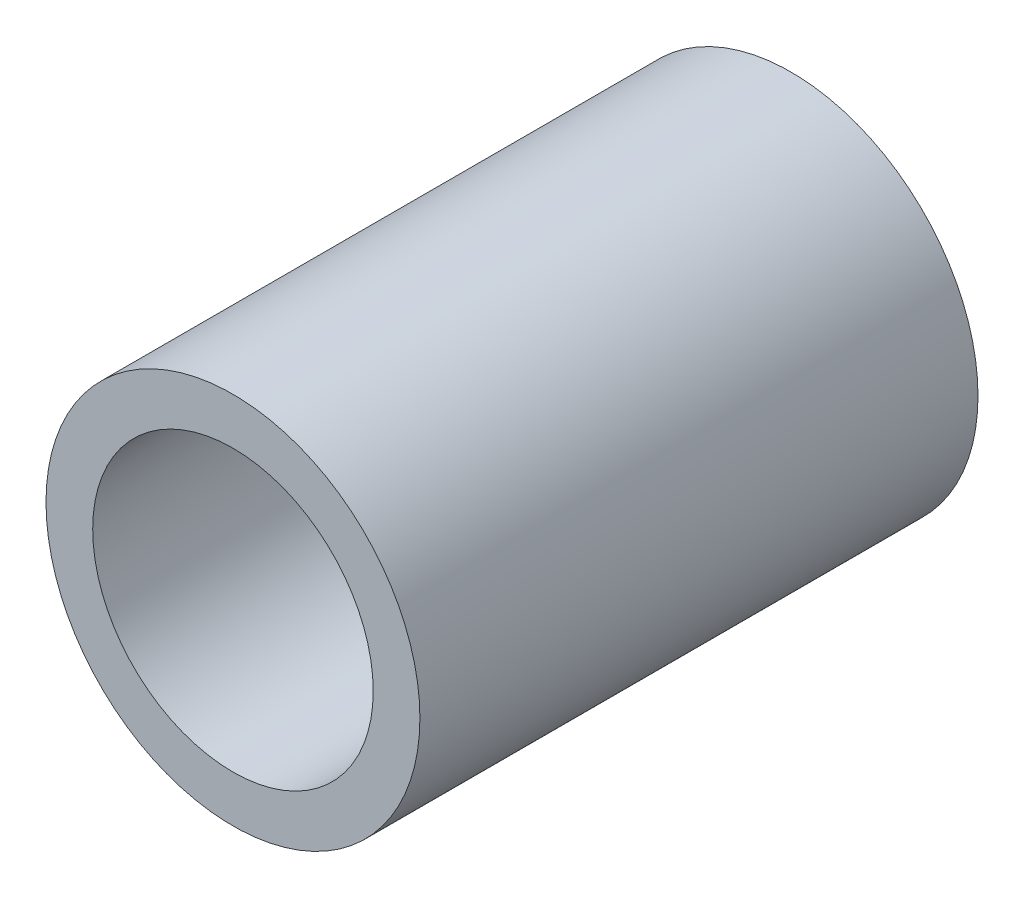
SolidWorks part; units mm, degrees
material "Brass"
ref_plane "Front Plane" through (0, 0, 0) normal (0, 0, 1) x (1, 0, 0)
ref_plane "Top Plane" through (0, 0, 0) normal (0, 1, 0) x (1, 0, 0)
ref_plane "Right Plane" through (0, 0, 0) normal (1, 0, 0) x (0, 0, -1)
sketch "Sketch1" plane through (0, 0, 0) normal (1, 0, 0) x (0, 0, -1)
  line L0 (-9.525, 6.3818) -> (-9.525, 4.7879)
  line L1 (-9.525, 4.7879) -> (9.525, 4.7879)
  line L2 (9.525, 4.7879) -> (9.525, 6.3818)
  line L3 (9.525, 6.3818) -> (-9.525, 6.3818)
  line L4 (9.525, 0) -> (-9.525, 0) construction
revolve "Revolve1" add sketch "Sketch1" angle 360 about L4 reverse direction yes
ref_plane "bushing XY" through (0, 0, 0) normal (0, 0, 1) x (1, 0, 0)
ref_plane "bushing XZ" through (0, 0, 0) normal (0, -1, 0) x (-1, 0, 0)
ref_plane "bushing YZ" through (0, 0, 0) normal (1, 0, 0) x (0, 0, -1)
ref_axis "bushing X" through (-80.9, 0, 0) along (1, 0, 0)
ref_axis "bushing Y" through (0, -50, 0) along (0, 1, 0)
ref_axis "bushing Z" through (0, 0, 80.9) along (0, 0, -1)
sketch3d "bushing"
  point P0 (0, 0, 0)
ref_plane "id1 XY" through (0, 0, 0) normal (0, 0, 1) x (1, 0, 0)
ref_plane "id1 XZ" through (0, 0, 0) normal (0, -1, 0) x (-1, 0, 0)
ref_plane "id1 YZ" through (-4.7879, 0, 0) normal (1, 0, 0) x (0, 0, -1)
ref_axis "id1 X" through (-80.9, 0, 0) along (1, 0, 0)
ref_axis "id1 Y" through (-4.7879, -50, 0) along (0, 1, 0)
ref_axis "id1 Z" through (-4.7879, 0, 80.9) along (0, 0, -1)
sketch3d "id1"
  point P0 (-4.7879, 0, 0)
ref_plane "id2 XY" through (0, 0, 0) normal (0, 0, 1) x (1, 0, 0)
ref_plane "id2 XZ" through (0, 0, 0) normal (0, -1, 0) x (-1, 0, 0)
ref_plane "id2 YZ" through (4.7879, 0, 0) normal (1, 0, 0) x (0, 0, -1)
ref_axis "id2 X" through (-80.9, 0, 0) along (1, 0, 0)
ref_axis "id2 Y" through (4.7879, -50, 0) along (0, 1, 0)
ref_axis "id2 Z" through (4.7879, 0, 80.9) along (0, 0, -1)
sketch3d "id2"
  point P0 (4.7879, 0, 0)
ref_plane "id3 XY" through (0, 0, -9.525) normal (0, 0, -1) x (-1, 0, 0)
ref_plane "id3 XZ" through (0, 0, 0) normal (-1, 0, 0) x (0, 0, 1)
ref_plane "id3 YZ" through (0, 0, 0) normal (0, 1, 0) x (1, 0, 0)
ref_axis "id3 X" through (0, -50, -9.525) along (0, 1, 0)
ref_axis "id3 Y" through (-80.9, 0, -9.525) along (1, 0, 0)
ref_axis "id3 Z" through (0, 0, -50) along (0, 0, 1)
sketch3d "id3"
  point P0 (0, 0, -9.525)
ref_plane "id4 XY" through (0, 0, 9.525) normal (0, 0, 1) x (1, 0, 0)
ref_plane "id4 XZ" through (0, 0, 0) normal (1, 0, 0) x (0, 0, -1)
ref_plane "id4 YZ" through (0, 0, 0) normal (0, 1, 0) x (1, 0, 0)
ref_axis "id4 X" through (0, -50, 9.525) along (0, 1, 0)
ref_axis "id4 Y" through (80.9, 0, 9.525) along (-1, 0, 0)
ref_axis "id4 Z" through (0, 0, 50) along (0, 0, -1)
sketch3d "id4"
  point P0 (0, 0, 9.525)
